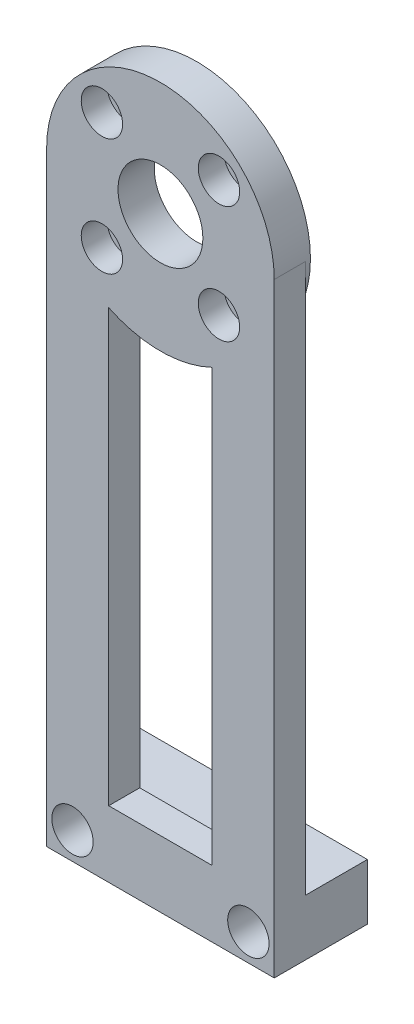
SolidWorks part; units mm, degrees
ref_plane "Front Plane" through (0, 0, 0) normal (0, 0, 1) x (1, 0, 0)
ref_plane "Top Plane" through (0, 0, 0) normal (0, 1, 0) x (1, 0, 0)
ref_plane "Right Plane" through (0, 0, 0) normal (1, 0, 0) x (0, 0, -1)
sketch "Sketch1" plane through (0, 0, 0) normal (0, 0, 1) x (1, 0, 0)
  line L0 (0, 29.235) -> (0, -29.235) construction
  line L2 (11, 29.235) -> (11, -29.235)
  line L4 (-11, 29.235) -> (-11, -29.235)
  line L5 (-11, -29.235) -> (11, -29.235)
  line L7 (11, -29.235) -> (-11, -29.235)
  line L8 (11, -29.235) -> (11, -23.815)
  line L9 (11, -23.815) -> (-11, -23.815)
  line L10 (-11, -29.235) -> (-11, -23.815)
  line L12 (-5, 18.8788) -> (-5, -22.815)
  line L13 (-5, -22.815) -> (5, -22.815)
  line L14 (5, 18.8788) -> (5, -22.815)
  circle A0 centre (0, 29.235) radius 11
  arc A1 (-5, 18.8788) -> (5, 18.8788) centre (0, 29.235) ccw
  point P0 (0, 0)
  point P2 (0, 0)
  point P8 (0, -29.235)
  dimension "D3" = 22
  dimension "D1" = 58.47
  dimension "D4" = 5.42
  dimension "D5" = 23
  dimension "D7" = 6
  dimension "D2" = 22
  dimension "D6" = 1
  dimension "D8" = 6
extrude "Boss-Extrude1" add sketch "Sketch1" along normal blind 3 contours L2 A0 L4 | A0 | A0 L0 L2 | L8 L7 L10 L9 region at (0, 29.235, 0) region at (10.4257, 2.71, 0)
extrude "Boss-Extrude2" add sketch "Sketch1<3>" against normal blind 0.5 contours A0 region at (0, 29.235, 0)
sketch "Sketch1<3>" plane through (0, 0, 0) normal (0, 0, 1) x (1, 0, 0) same geometry as "Sketch1"
sketch "Sketch2" plane through (0, 0, 3) normal (0, 0, 1) x (1, 0, 0)
  line L0 (0, 29.235) -> (5.6569, 34.8919) construction
  line L1 (11, 29.235) -> (11, -29.235) construction
  circle A0 centre (0, 29.235) radius 4.1
  circle A1 centre (5.6569, 34.8919) radius 1.1
  circle A2 centre (5.6569, 34.8919) radius 2
  dimension "D1" = 8.2
  dimension "D2" = 2.2
  dimension "D5" = 4
  dimension "D3" = 8
  dimension "D4" = 45
extrude "Cut-Extrude1" cut sketch "Sketch2" against normal up to surface (3.5 mm away) contours A0 | A1 region at (0, 29.235, 3) region at (5.6569, 34.8919, 3) up to face at (11, 29.235, -0.5)
extrude "Cut-Extrude2" cut sketch "Sketch2<3>" against normal offset from surface (2.5 mm away) 1 contours A2 A1 region at (3.7134, 34.8919, 3) up to face at (4.1, 29.235, -0.5)
sketch "Sketch2<3>" plane through (0, 0, 3) normal (0, 0, 1) x (1, 0, 0) same geometry as "Sketch2"
pattern_circular "CirPattern2" count 4 over 360 about axis through (0, 29.235, 3) along (0, 0, 1) of "Cut-Extrude2", "Cut-Extrude1"
extrude "Boss-Extrude3" add sketch "Sketch1<6>" against normal blind 6 contours L0 L9 L4 L5 | L9 L0 L7 L2 region at (-5.5, -26.525, 0) region at (5.5, -26.525, 0)
sketch "Sketch1<6>" plane through (0, 0, 0) normal (0, 0, 1) x (1, 0, 0) same geometry as "Sketch1"
sketch "Sketch3" plane through (0, 0, 3) normal (0, 0, 1) x (1, 0, 0)
  line L0 (-8.5, -26.6202) -> (8.5, -26.6202) construction
  line L1 (-11, -29.235) -> (11, -29.235) construction
  circle A0 centre (-8.5, -26.6202) radius 1.1
  circle A1 centre (8.5, -26.6202) radius 1.1
  circle A2 centre (-8.5, -26.6202) radius 2
  circle A3 centre (8.5, -26.6202) radius 2
  point P4 (0, -26.6202)
  dimension "D1" = 2.2
  dimension "D4" = 4
  dimension "D2" = 17
  dimension "D3" = 2.6148
extrude "Cut-Extrude3" cut sketch "Sketch3" against normal up to surface (9 mm away) contours A0 | A1 region at (-8.5, -26.6202, 3) region at (8.5, -26.6202, 3) up to face at (0, -26.525, -6)
extrude "Cut-Extrude4" cut sketch "Sketch3<3>" against normal offset from surface (8 mm away) 1 up to face at (-7.4, -26.6202, -6)
sketch "Sketch3<3>" plane through (0, 0, 3) normal (0, 0, 1) x (1, 0, 0) same geometry as "Sketch3"
